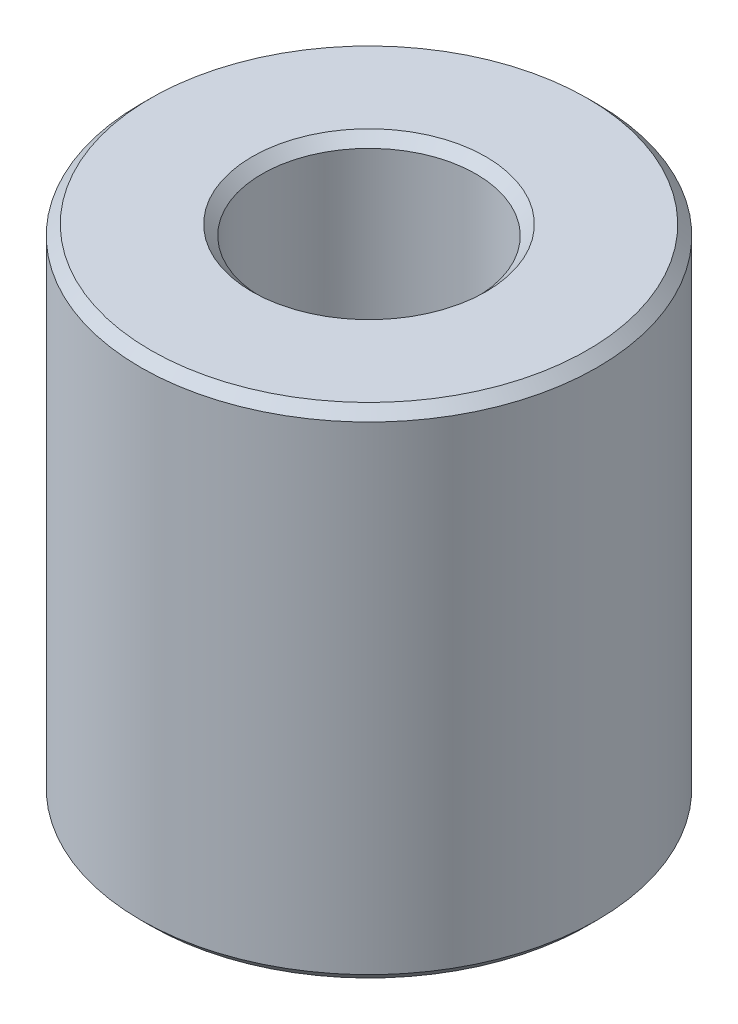
SolidWorks part; units mm, degrees
ref_plane "Front Plane" through (0, 0, 0) normal (0, 0, 1) x (1, 0, 0)
ref_plane "Top Plane" through (0, 0, 0) normal (0, 1, 0) x (1, 0, 0)
ref_plane "Right Plane" through (0, 0, 0) normal (1, 0, 0) x (0, 0, -1)
sketch "Sketch1" plane through (0, 0, 0) normal (0, 1, 0) x (1, 0, 0)
  circle A0 centre (0, 0) radius 5
  dimension "SLEEVE_OD" = 10
extrude "Boss-Extrude1" add sketch "Sketch1" along normal blind 10.9187
sketch "Sketch2" plane through (0, 0, 0) normal (0, 1, 0) x (1, 0, 0)
  circle A0 centre (0, 0) radius 2.3438
  dimension "BORE_D" = 4.6876
extrude "Cut-Extrude1" cut sketch "Sketch2" along normal through all
chamfer "Chamfer1" distance 0.2178 angle 45 4 edges at (0, 10.9187, 2.3438) (0, 0, 2.3438) (0, 0, 5) (0, 10.9187, 5)
